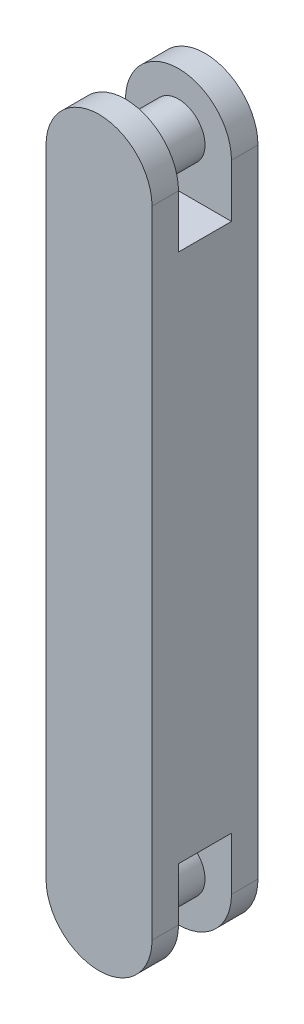
SolidWorks part; units mm, degrees
ref_plane "Front Plane" through (0, 0, 0) normal (0, 0, 1) x (1, 0, 0)
ref_plane "Top Plane" through (0, 0, 0) normal (0, 1, 0) x (1, 0, 0)
ref_plane "Right Plane" through (0, 0, 0) normal (1, 0, 0) x (0, 0, -1)
sketch "Sketch1" plane through (0, 0, 0) normal (0, 0, 1) x (1, 0, 0)
  line L0 (0, 0) -> (0, 304.8) construction
  line L1 (-25.4, 0) -> (-25.4, 304.8)
  line L2 (25.4, 0) -> (25.4, 304.8)
  circle A0 centre (0, 0) radius 12.7
  arc A1 (-25.4, 0) -> (25.4, 0) centre (0, 0) ccw
  arc A2 (25.4, 304.8) -> (-25.4, 304.8) centre (0, 304.8) ccw
  circle A3 centre (0, 304.8) radius 12.7
  point P4 (0, 152.4)
  point P11 (0, 0)
  point P12 (0, 304.8)
  dimension "D1" = 25.4
  dimension "D2" = 25.4
  dimension "D3" = 304.8
extrude "Boss-Extrude1" add sketch "Sketch1" along normal mid plane 50.8
sketch "Sketch2" plane through (0, 0, 0) normal (1, 0, 0) x (0, 0, -1)
  line L0 (25.4, 330.2) -> (-25.4, 330.2) construction
  line L1 (-12.7, 330.2) -> (12.7, 330.2)
  line L2 (-12.7, 330.2) -> (-12.7, 279.4)
  line L3 (-12.7, 279.4) -> (12.7, 279.4)
  line L4 (12.7, 330.2) -> (12.7, 279.4)
  line L5 (-25.4, -25.4) -> (25.4, -25.4) construction
  line L6 (-12.7, -25.4) -> (12.7, -25.4)
  line L7 (-12.7, -25.4) -> (-12.7, 25.4)
  line L8 (-12.7, 25.4) -> (12.7, 25.4)
  line L9 (12.7, -25.4) -> (12.7, 25.4)
  point P6 (0, 330.2)
  dimension "D1" = 25.4
  dimension "D2" = 50.8
extrude "Cut-Extrude1" cut sketch "Sketch2" against normal through all both and the other way through all
extrude "Boss-Extrude2" add sketch "Sketch1<2>" against normal up to surface and the other way up to surface contours A0 | A3 region at (0, 0, 0) region at (0, 304.8, 0) up to face at (0, 152.4, -25.4) other way up to face at (12.7, 0, 25.4)
sketch "Sketch1<2>" plane through (0, 0, 0) normal (0, 0, 1) x (1, 0, 0) same geometry as "Sketch1"
